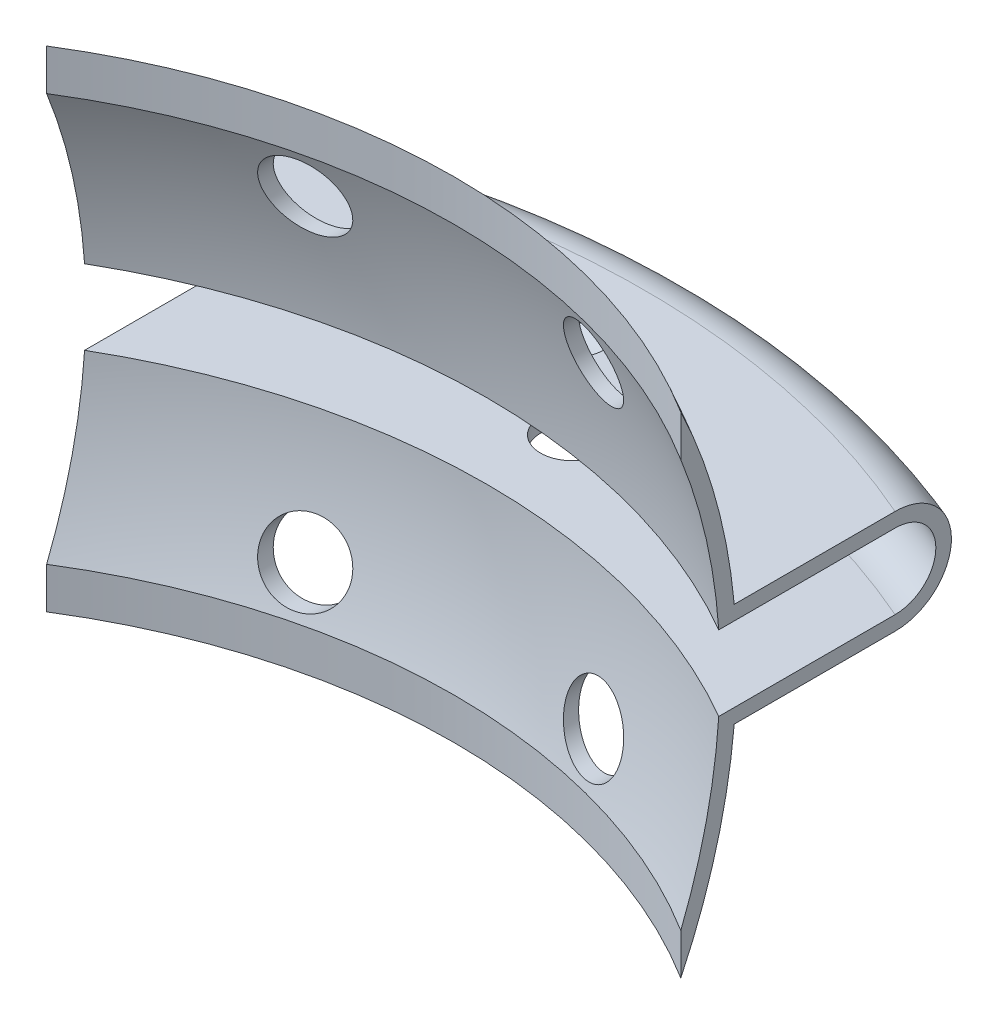
SolidWorks part; units mm, degrees
material "Plain Carbon Steel"
ref_plane "Front Plane" through (0, 0, 0) normal (0, 0, 1) x (1, 0, 0)
ref_plane "Top Plane" through (0, 0, 0) normal (0, 1, 0) x (1, 0, 0)
ref_plane "Right Plane" through (0, 0, 0) normal (1, 0, 0) x (0, 0, -1)
sketch "Sketch1" plane through (0, 0, 0) normal (0, 0, 1) x (1, 0, 0)
  line L0 (0, 250) -> (0, -250) construction
  line L1 (-208.3267, -85) -> (-208.3267, 85)
  line L2 (-1134.9127, 0) -> (311.0396, 0) construction
  line L3 (-274.2788, -18) -> (-224.2788, -18)
  line L4 (-274.2788, -18) -> (-274.2788, 18) construction
  line L5 (-274.2788, 18) -> (-224.2788, 18)
  arc A0 (-208.3267, -85) -> (-224.2788, -18) centre (0, 0) cw
  arc A1 (-274.2788, -18) -> (-274.2788, 18) centre (-274.2788, 0) cw
  arc A2 (-224.2788, 18) -> (-208.3267, 85) centre (0, 0) cw
  dimension "D1" = 225
  dimension "D2" = 50
  dimension "D3" = 170
  dimension "D4" = 36
revolve "Revolve1" add sketch "Sketch1" angle 180 about L0
shell "Shell1" thickness 5 removed face at (0, 0, -104.1633)
sketch "Sketch2" plane through (0, 0, 0) normal (0, 0, 1) x (1, 0, 0)
  line L17 (-203.6972, 83.1111) -> (-203.6972, -83.1111)
  line L18 (0, 835.3833) -> (0, -835.3833) construction
  line L19 (-274.2788, -13) -> (-219.6156, -13)
  line L20 (-219.6156, 13) -> (-274.2788, 13)
  line L21 (-274.2788, -13) -> (-219.6156, -13)
  line L22 (-219.6156, 13) -> (-274.2788, 13)
  arc A22 (-203.6972, 83.1111) -> (-219.6156, 13) centre (0, 0) ccw
  arc A23 (-219.6156, -13) -> (-203.6972, -83.1111) centre (0, 0) ccw
  arc A24 (-274.2788, 13) -> (-274.2788, -13) centre (-274.2788, 0) ccw
  arc A25 (-203.6972, 83.1111) -> (-219.6156, 13) centre (0, 0) ccw
  arc A26 (-219.6156, -13) -> (-203.6972, -83.1111) centre (0, 0) ccw
  arc A27 (-274.2788, 13) -> (-274.2788, -13) centre (-274.2788, 0) ccw
  point P2 (0, 0)
  dimension "D1" = 5
revolve "Cut-Revolve1" cut sketch "Sketch2" about L18
hole_wizard "M24 Clearance Hole4" positions "Sketch5" profile "Sketch7" hole size "M24" standard "ANSI Metric" end condition through all
sketch "Sketch5" plane through (0, 0, 0) normal (0, 0, -1) x (-1, 0, 0)
  line L0 (-478.2857, 0) -> (592.2697, 0) construction
  line L2 (0, 481.6382) -> (0, -486.1082) construction
  point P0 (-50, 55)
  dimension "D1" = 110
  dimension "D2" = 100
sketch "Sketch7" plane through (50, 55, 0) normal (1, 0, 0) x (0, -1, 0)
  line L0 (0, 0) -> (0, 292.2788)
  line L1 (0, 292.2788) -> (13, 292.2788)
  line L2 (13, 292.2788) -> (13, 0)
  line L5 (13, 0) -> (0, 0)
  line L11 (0, -6.35) -> (0, 107.95) construction
  dimension "Thru Hole Dia." = 26
  dimension "Thru Hole Depth" = 292.2788
sketch "Sketch10" plane through (0, 0, 0) normal (0, 0, 1) x (1, 0, 0)
  line L0 (0, 612.723) -> (0, -277.4428) construction
  line L1 (110, 250) -> (840, 250)
  line L2 (110, 250) -> (110, -250)
  line L3 (110, -250) -> (840, -250)
  line L4 (840, 250) -> (840, -250)
  line L5 (110, 250) -> (840, -250) construction
  line L6 (110, -250) -> (840, 250) construction
  line L7 (-110, -250) -> (-840, 250) construction
  line L8 (-110, 250) -> (-840, -250) construction
  line L9 (-840, 250) -> (-840, -250)
  line L10 (-110, -250) -> (-840, -250)
  line L11 (-110, 250) -> (-110, -250)
  line L12 (-110, 250) -> (-840, 250)
  point P0 (475, 0)
  point P13 (-475, 0)
  dimension "D1" = 110
  dimension "D2" = 730
  dimension "D3" = 500
extrude "Cut-Extrude1" cut sketch "Sketch10" against normal through all
sketch "Sketch11" plane through (0, -18, 0) normal (0, -1, 0) x (1, 0, 0)
  line L0 (0, -224.2788) -> (0, -274.2788) construction
  circle A1 centre (0, -249.2788) radius 21
  arc A2 (-110, -195.4508) -> (110, -195.4508) centre (0, 0) ccw construction
  arc A3 (-110, -251.2546) -> (110, -251.2546) centre (0, 0) ccw construction
  point P13 (0, -249.2788)
  dimension "D1" = 42
hole_wizard "M20 Clearance Hole1" positions "Sketch12" profile "Sketch13" hole size "M20" standard "ANSI Metric" end condition through all
sketch "Sketch12" plane through (0, -18, 0) normal (0, -1, 0) x (-1, 0, 0)
  point P0 (0, 249.2788)
sketch "Sketch13" plane through (0, -18, -249.2788) normal (1, 0, 0) x (0, 0, -1)
  line L0 (0, 0) -> (0, 103)
  line L1 (0, 103) -> (11, 103)
  line L2 (11, 103) -> (11, 0)
  line L5 (11, 0) -> (0, 0)
  line L11 (0, -6.35) -> (0, 107.95) construction
  dimension "Thru Hole Dia." = 22
  dimension "Thru Hole Depth" = 103
pattern_linear "LPattern2" count 2 spacing 110 along (0, -1, 0) count 2 spacing 100 along (-1, 0, 0) of "M24 Clearance Hole4"
scale "Ölçek1" bodies to scale 108 scale about centroid uniform scaling yes scale factor 0.1
